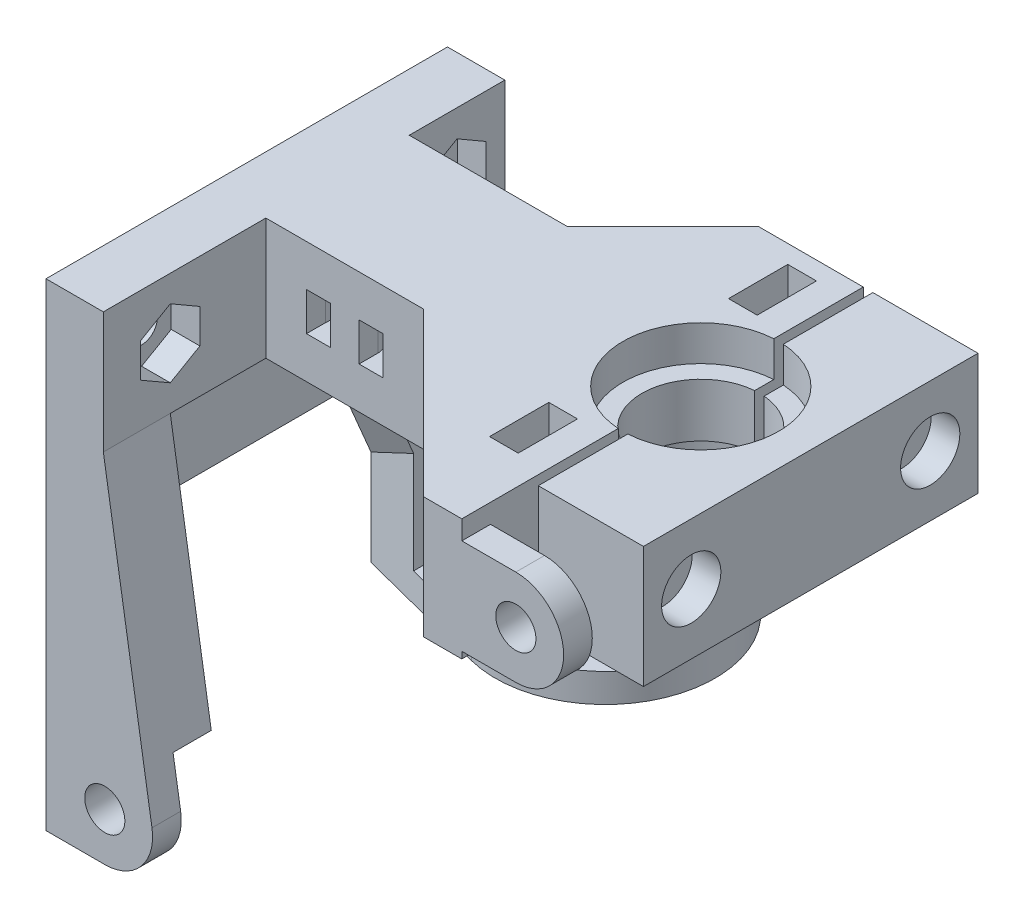
SolidWorks part; units mm, degrees
note: The reader was unsure of these and kept them because the rebuilt part matched: shared geometry of "草圖14<3>", "草圖43<3>", "草圖34<5>", "草圖48<3>".
ref_plane "前基準面" through (0, 0, 0) normal (0, 0, 1) x (1, 0, 0)
ref_plane "上基準面" through (0, 0, 0) normal (0, 1, 0) x (1, 0, 0)
ref_plane "右基準面" through (0, 0, 0) normal (1, 0, 0) x (0, 0, -1)
sketch "草圖13" plane through (0, 0, 0) normal (0, 1, 0) x (1, 0, 0)
  line L0 (0, 0) -> (44, 0) construction
  line L1 (0, 0) -> (0, 17.5)
  line L2 (0, 0) -> (0, -17.5)
  line L3 (0, 17.5) -> (6, 17.5)
  line L4 (6, 17.5) -> (6, -17.5)
  line L5 (6, -17.5) -> (0, -17.5)
  line L6 (6, 7.5) -> (32.5, 7.5)
  line L7 (6, -7.5) -> (32.5, -7.5)
  line L8 (32.5, 17.5) -> (22.5, 7.5)
  line L9 (32.5, -17.5) -> (55.5, -17.5)
  line L10 (32.5, -17.5) -> (32.5, 17.5)
  line L11 (32.5, 17.5) -> (55.5, 17.5)
  line L12 (55.5, -17.5) -> (55.5, 17.5)
  line L13 (32.5, -17.5) -> (55.5, 17.5) construction
  line L14 (32.5, 17.5) -> (55.5, -17.5) construction
  line L15 (32.5, -17.5) -> (22.5, -7.5)
  line L16 (32.5, 7.5) -> (22.5, 7.5)
  line L17 (22.5, -7.5) -> (32.5, -7.5)
  circle A0 centre (44, 0) radius 8.15
  circle A1 centre (44, 0) radius 6.15
  point P17 (44, 0)
  dimension "D4" = 35
  dimension "D5" = 12.3
  dimension "D6" = 23
  dimension "D1" = 16.3
  dimension "D2" = 35
  dimension "D3" = 6
  dimension "D7" = 15
  dimension "D8" = 10
  dimension "D9" = 44
extrude "填料-伸長4" add sketch "草圖13" against normal blind 12.7
sketch "草圖17" plane through (0, 0, 0) normal (0, 1, 0) x (1, 0, 0)
  circle A0 centre (44, 0) radius 6.15
  circle A1 centre (44, 0) radius 8.15
  circle A2 centre (44, 0) radius 6.15 construction
  circle A3 centre (44, 0) radius 8.15 construction
  circle M29 centre (44, 0) radius 6.15
ref_plane "平面4" through (44, 0, 0) normal (-1, 0, 0) x (0, 0, 1)
sketch "草圖14" plane through (55.5, 0, 0) normal (-1, 0, 0) x (0, 0, 1)
  line L0 (17.5, -6.35) -> (7.5, -6.35) construction
  line L3 (-7.5, -6.35) -> (-17.5, -6.35) construction
  line L5 (-17.5, -12.7) -> (-17.5, 0) construction
  line L6 (17.5, -12.7) -> (17.5, 0) construction
  line L9 (7.5, -12.7) -> (7.5, 0) construction
  line L10 (-7.5, -12.7) -> (-7.5, 0) construction
  circle A0 centre (-12.5, -6.35) radius 1.65
  circle A1 centre (12.5, -6.35) radius 1.65
  circle A2 centre (12.5, -6.35) radius 3.1
  circle A3 centre (-12.5, -6.35) radius 3.1
  dimension "D1" = 3.3
  dimension "D2" = 6.2
sketch "草圖15" plane through (44, 0, 0) normal (-1, 0, 0) x (0, 0, 1)
  line L1 (17.5, 0) -> (-17.5, 0)
  line L2 (17.5, 0) -> (17.5, -12.7)
  line L3 (17.5, -12.7) -> (-17.5, -12.7)
  line L4 (-17.5, 0) -> (-17.5, -12.7)
extrude "除料-伸長11" cut sketch "草圖15" against normal blind 0.5 and the other way blind 0.5
extrude "除料-伸長12" cut sketch "草圖14" along normal blind 3 contours A3 A0 | A2 A1
extrude "除料-伸長13" cut sketch "草圖14<3>" along normal blind 25 contours A0 | A1
sketch "草圖14<3>" plane through (55.5, 0, 0) normal (-1, 0, 0) x (0, 0, 1) same geometry as "草圖14"
ref_plane "平面5" through (37.5, 0, 0) normal (1, 0, 0) x (0, 0, -1)
sketch "草圖16" plane through (37.5, 0, 0) normal (1, 0, 0) x (0, 0, -1)
  line L0 (-17.5, 0) -> (17.5, 0) construction
  line L1 (-15.6, -12.7) -> (-9.4, -12.7)
  line L2 (-15.6, -12.7) -> (-15.6, 0)
  line L3 (-15.6, 0) -> (-9.4, 0)
  line L4 (-9.4, -12.7) -> (-9.4, 0)
  line L5 (-15.6, -12.7) -> (-9.4, 0) construction
  line L6 (-15.6, 0) -> (-9.4, -12.7) construction
  line L8 (9.4, -12.7) -> (15.6, -12.7)
  line L9 (9.4, -12.7) -> (9.4, 0)
  line L10 (9.4, 0) -> (15.6, 0)
  line L11 (15.6, -12.7) -> (15.6, 0)
  line L12 (9.4, -12.7) -> (15.6, 0) construction
  line L13 (9.4, 0) -> (15.6, -12.7) construction
  point P0 (-12.5, -6.35)
  point P8 (12.5, -6.35)
  dimension "D1" = 6.2
extrude "除料-伸長14" cut sketch "草圖16" along normal blind 3
extrude "除料-伸長30" cut sketch "草圖17" against normal blind 3.7 contours A1 M29
sketch "草圖18" plane through (0, -12.7, 0) normal (0, -1, 0) x (1, 0, 0)
  circle A0 centre (44, 0) radius 8.15
  circle A1 centre (44, 0) radius 8.15 construction
  circle A2 centre (44, 0) radius 6.15
  circle A3 centre (44, 0) radius 6.15 construction
  line M5 (43.5, 6.1296) -> (43.5, 17.5)
  line M17 (43.5, -17.5) -> (43.5, -6.1296)
  arc M18 (43.5, -6.1296) -> (43.5, 6.1296) centre (44, 0) cw
extrude "除料-伸長31" cut sketch "草圖18" against normal blind 3.4 contours A2 A0 M17 M5 | A0 M5 M17 M18
sketch "草圖19" plane through (0, 0, 0) normal (-1, 0, 0) x (0, 0, 1)
  line L0 (0, 0) -> (0, -12.7) construction
  line L1 (17.5, -12.7) -> (-17.5, -12.7) construction
  line L2 (-12.5, -6.35) -> (12.5, -6.35) construction
  circle A0 centre (-12.5, -6.35) radius 1.65
  circle A1 centre (12.5, -6.35) radius 1.65
  point P8 (0, -6.35)
  dimension "D2" = 3.3
  dimension "D1" = 25
extrude "除料-伸長32" cut sketch "草圖19" against normal up to surface (6 mm away) contours A0 up to face at (6, -6.35, 12.5)
sketch "草圖20" plane through (6, 0, 0) normal (1, 0, 0) x (0, 0, -1)
  line L1 (-12.5, -2.8282) -> (-15.55, -4.5891)
  line L2 (-15.55, -4.5891) -> (-15.55, -8.1109)
  line L3 (-15.55, -8.1109) -> (-12.5, -9.8718)
  line L4 (-12.5, -9.8718) -> (-9.45, -8.1109)
  line L5 (-9.45, -8.1109) -> (-9.45, -4.5891)
  line L6 (-9.45, -4.5891) -> (-12.5, -2.8282)
  line L7 (12.5, -2.8282) -> (9.45, -4.5891)
  line L8 (9.45, -4.5891) -> (9.45, -8.1109)
  line L9 (9.45, -8.1109) -> (12.5, -9.8718)
  line L10 (12.5, -9.8718) -> (15.55, -8.1109)
  line L11 (15.55, -8.1109) -> (15.55, -4.5891)
  line L12 (15.55, -4.5891) -> (12.5, -2.8282)
  circle A0 centre (-12.5, -6.35) radius 3.05 construction
  circle A1 centre (12.5, -6.35) radius 3.05 construction
  dimension "D1" = 6.1
extrude "除料-伸長33" cut sketch "草圖20" against normal blind 3 contours L11 L12 L7 L8 L9 L10
sketch "草圖21" plane through (0, -12.7, 0) normal (0, -1, 0) x (1, 0, 0)
  line L0 (0, -17.5) -> (6, -17.5) construction
  line L1 (0, 17.5) -> (3, 17.5)
  line L2 (0, 17.5) -> (0, -17.5)
  line L3 (0, -17.5) -> (3, -17.5)
  line L4 (3, 17.5) -> (3, -17.5)
  dimension "D1" = 3
extrude "填料-伸長5" add sketch "草圖21" along normal blind 10
ref_plane "平面6" through (0, 0, 24.5) normal (0, 0, 1) x (1, 0, 0)
sketch "草圖22" plane through (0, 0, 24.5) normal (0, 0, 1) x (1, 0, 0)
  line L0 (0, 0) -> (0, -50)
  line L1 (0, -50) -> (6.15, -50)
  line L2 (6.15, -45) -> (49.15, -45) construction
  line L3 (49.15, -45) -> (49.15, -7) construction
  line L4 (0, 0) -> (6, 0)
  line L5 (6, -12.7) -> (11.0861, -44.2031)
  line L6 (6, 0) -> (6, -12.7)
  line L8 (49.15, -2) -> (43.5, -2)
  line L10 (43.5, -12.7) -> (43.5, 0) construction
  line L11 (43.5, -2) -> (43.5, 0)
  line L13 (43.5, 0) -> (38, 0)
  line L14 (32.5, 0) -> (43.5, 0) construction
  line L15 (38, 0) -> (38, -12.7)
  line L16 (32.5, -12.7) -> (43.5, -12.7) construction
  line L17 (38, -12.7) -> (43.5, -12.7)
  line L18 (43.5, -12.7) -> (43.5, -12)
  line L19 (43.5, -12) -> (49.15, -12)
  circle A0 centre (49.15, -7) radius 2.1
  circle A1 centre (6.15, -45) radius 2.1
  circle A2 centre (6.15, -45) radius 5
  circle A3 centre (49.15, -7) radius 5
  dimension "D5" = 4.2
  dimension "D4" = 10
  dimension "D1" = 38
  dimension "D2" = 43
  dimension "D3" = 45
  dimension "D6" = 6.15
ref_plane "平面9" through (0, -6.35, 0) normal (0, 1, 0) x (1, 0, 0)
extrude "填料-伸長6" add sketch "草圖22" against normal up to surface (7 mm away)
sketch "草圖41" plane through (0, 0, 17.5) normal (0, 0, -1) x (-1, 0, 0)
  line L1 (-13.6797, -50.7245) -> (1.3797, -50.7245)
  line L2 (-13.6797, -50.7245) -> (-13.6797, -39.2755)
  line L3 (-13.6797, -39.2755) -> (1.3797, -39.2755)
  line L4 (1.3797, -50.7245) -> (1.3797, -39.2755)
  line L5 (-13.6797, -50.7245) -> (1.3797, -39.2755) construction
  line L6 (-13.6797, -39.2755) -> (1.3797, -50.7245) construction
  point P0 (-6.15, -45)
extrude "除料-伸長34" cut sketch "草圖41" against normal blind 4
sketch "草圖42" plane through (0, -2, 0) normal (0, 1, 0) x (1, 0, 0)
  line L0 (54.15, -24.5) -> (54.15, -17.5) construction
  line L1 (43.5, -17.5) -> (54.15, -17.5)
  line L2 (43.5, -17.5) -> (43.5, -21.5)
  line L3 (43.5, -21.5) -> (54.15, -21.5)
  line L4 (54.15, -17.5) -> (54.15, -21.5)
  dimension "D1" = 4
extrude "除料-伸長35" cut sketch "草圖42" against normal up to surface (10 mm away) up to face at (45.96, -12, 20.3)
sketch "草圖43" plane through (0, 0, 0) normal (0, 1, 0) x (1, 0, 0)
  line L0 (32.5, -17.5) -> (39.5, -24.5)
  line L1 (43.5, -24.5) -> (38, -24.5) construction
  line L2 (39.5, -24.5) -> (32.5, -24.5)
  line L3 (32.5, -17.5) -> (32.5, -24.5)
  line L4 (32.5, -17.5) -> (38, -17.5)
  line L5 (38, -17.5) -> (38, -23)
  line L6 (38, -17.5) -> (38, -24.5) construction
  line L7 (32.5, -17.5) -> (22.5, -7.5) construction
  line M16 (32.5, -17.5) -> (38, -17.5)
  line M17 (38, -17.5) -> (38, -24.5)
  line M18 (38, -24.5) -> (43.5, -24.5)
extrude "除料-伸長36" cut sketch "草圖43" against normal up to surface (12.7 mm away) contours L0 M17 M18 up to face at (23.8969, -12.7, 1.9688)
extrude "填料-伸長7" add sketch "草圖43<3>" against normal up to surface (12.7 mm away) contours L0 M16 M17 up to face at (39, -12.7, -12.5)
sketch "草圖43<3>" plane through (0, 0, 0) normal (0, 1, 0) x (1, 0, 0) same geometry as "草圖43"
sketch "草圖34" plane through (6, 0, 0) normal (1, 0, 0) x (0, 0, -1)
  line L0 (17.5, -12.7) -> (9.5, -12.7)
  line L1 (9.5, -22.7) -> (9.5, -42.7)
  line L2 (9.5, -42.7) -> (24.5, -42.7)
  line L3 (17.5, -16.2009) -> (24.5, -32.7)
  line L4 (17.5, -12.7) -> (8.1346, -12.7) construction
  line L5 (9.5, -12.7) -> (9.5, -22.7)
  line L6 (9.5, -32.7) -> (5.2574, -22.7)
  line L7 (17.5, -12.7) -> (24.5, -12.7)
  line L8 (24.5, -12.7) -> (24.5, -42.7)
  line L9 (17.5, -22.7) -> (-17.5, -22.7) construction
  line L10 (5.2574, -22.7) -> (9.5, -22.7)
  line L11 (17.5, -22.7) -> (17.5, -12.7) construction
  line L12 (-17.5, -12.7) -> (17.5, -12.7) construction
  line L13 (5.2574, -22.7) -> (5.2574, -12.7)
  line L14 (-8.1346, -12.7) -> (8.1346, -12.7) construction
  line L15 (5.2574, -12.7) -> (9.5, -12.7)
  line L16 (9.5, -12.7) -> (9.4752, -12.712)
  line L17 (17.5, -12.7) -> (17.5, -16.2009)
  line L18 (9.5, -22.7) -> (17.5, -22.7)
  line L19 (17.5, -22.7) -> (17.5, -16.2009)
  dimension "D1" = 20
  dimension "D2" = 3.5009
  dimension "D3" = 8
  dimension "D4" = 10
  dimension "D5" = 20
  dimension "D6" = 7
extrude "填料-伸長8" add sketch "草圖34" against normal up to surface (6 mm away) contours L19 L18 L1 L2 L8 L3 | L10 L6 L1
sketch "草圖44" plane through (0, -42.7, 0) normal (0, -1, 0) x (1, 0, 0)
  line L0 (0, -24.5) -> (14.134, -28.1372)
  line L1 (0, -9.5) -> (14.134, -5.8628)
  line L2 (0, -9.5) -> (0, -24.5)
  line L5 (0, -9.5) -> (6, -9.5) construction
  line L6 (0, -24.5) -> (0, -9.5) construction
  circle A0 centre (17, -17) radius 11.5
  circle A1 centre (17, -17) radius 6.5
  line M1 (0, -9.5) -> (0, -24.5)
  line M2 (0, -24.5) -> (6, -24.5)
  line M3 (6, -24.5) -> (6, -9.5)
  line M4 (6, -9.5) -> (0, -9.5)
  dimension "D2" = 13
  dimension "D3" = 23
  dimension "D1" = 17
  dimension "D4" = 17
extrude "填料-伸長9" add sketch "草圖44" against normal blind 3 contours A0 A1 M3 | A0 M3 | A0 M3 M4 M1 M2 | A0 L0 M3 M2 | A0 L1 M4 M3
extrude "填料-伸長14" add sketch "草圖34<5>" against normal up to surface (3 mm away) up to face at (3, -19.9501, -6.7096)
sketch "草圖34<5>" plane through (6, 0, 0) normal (1, 0, 0) x (0, 0, -1) same geometry as "草圖34"
sketch "草圖39" plane through (0, -6.35, 0) normal (0, 1, 0) x (1, 0, 0)
  line L0 (6, -7.5) -> (14.25, -7.5) construction
  line L1 (6, -7.5) -> (22.5, -7.5) construction
  line L2 (14.25, -7.5) -> (14.25, -5.5) construction
  line L3 (12.75, -5.5) -> (12.75, -7.5)
  line L4 (15.75, -5.5) -> (15.75, -7.5)
  line L5 (10.25, -5.5) -> (10.25, -7.5)
  line L6 (13.25, -5.5) -> (13.25, -7.5)
  line L7 (18.25, -5.5) -> (18.25, -7.5)
  line L8 (15.75, -7.5) -> (18.25, -7.5)
  line L9 (10.25, -7.5) -> (12.75, -7.5)
  circle A0 centre (14.25, -5.5) radius 1.5
  circle A1 centre (14.25, -5.5) radius 4
  dimension "D2" = 3
  dimension "D1" = 2
  dimension "D3" = 2.5
extrude "除料-伸長37" cut sketch "草圖39" against normal blind 2 and the other way blind 2 contours L8 A1 L9 L3 A0 L4 | A1 L5 L9 | A1 L8 L7
sketch "草圖46" plane through (52.5, 0, 0) normal (1, 0, 0) x (0, 0, -1)
  circle A0 centre (-12.5, -6.35) radius 1.65
  circle A1 centre (12.5, -6.35) radius 1.65
extrude "填料-伸長12" add sketch "草圖46" against normal blind 0.2
sketch "草圖47" plane through (40.5, 0, 0) normal (-1, 0, 0) x (0, 0, 1)
  circle A0 centre (12.5, -6.35) radius 1.65
  circle A1 centre (-12.5, -6.35) radius 1.65
extrude "填料-伸長13" add sketch "草圖47" against normal blind 0.2
sketch "草圖48" plane through (0, -39.7, 0) normal (0, 1, 0) x (1, 0, 0)
  line L0 (6, 24.5) -> (6, 26.044)
  line L1 (0, 24.5) -> (14.134, 28.1372) construction
  line L2 (6, 26.044) -> (0, 24.5)
  line L3 (0, 24.5) -> (6, 24.5)
  line L4 (0, 9.5) -> (6, 7.956)
  line L5 (6, 17.5) -> (6, 7.5) construction
  line L6 (0, 9.5) -> (14.134, 5.8628) construction
  line L7 (6, 7.956) -> (6, 9.5)
  line L8 (0, 9.5) -> (6, 9.5)
  line M1 (6, 9.5) -> (0, 9.5)
  line M2 (0, 9.5) -> (14.134, 5.8628)
  line M4 (14.134, 28.1372) -> (0, 24.5)
  line M5 (0, 24.5) -> (6, 24.5)
extrude "填料-伸長15" add sketch "草圖48" along normal up to surface (3.3608 mm away) contours L0 M5 M4
extrude "填料-伸長16" add sketch "草圖48<3>" along normal up to surface (7 mm away) contours L7 M2 M1
sketch "草圖48<3>" plane through (0, -39.7, 0) normal (0, 1, 0) x (1, 0, 0) same geometry as "草圖48"
sketch "草圖49" plane through (0, 0, 0) normal (-1, 0, 0) x (0, 0, 1)
  line L0 (-12.5, -6.35) -> (17.5, -6.35) construction
  circle A0 centre (17.5, -6.35) radius 1.65
  circle A1 centre (-12.5, -6.35) radius 1.65 construction
  dimension "D1" = 30
extrude "除料-伸長38" cut sketch "草圖49" against normal up to surface (6 mm away) up to face at (6, -7.62, 16.3)
sketch "草圖50" plane through (6, 0, 0) normal (1, 0, 0) x (0, 0, -1)
  line L0 (-17.5, -12.7) -> (-17.5, 0) construction
  line L1 (-17.5, -2.7704) -> (-20.6, -4.5602)
  line L2 (-20.6, -4.5602) -> (-20.6, -8.1398)
  line L3 (-20.6, -8.1398) -> (-17.5, -9.9296)
  line L4 (-17.5, -9.9296) -> (-14.4, -8.1398)
  line L5 (-14.4, -8.1398) -> (-14.4, -4.5602)
  line L6 (-14.4, -4.5602) -> (-17.5, -2.7704)
  circle A0 centre (-17.5, -6.35) radius 3.1 construction
  circle A1 centre (12.5, -6.35) radius 3.1 construction
  circle M3 centre (-17.5, -6.35) radius 1.65
extrude "除料-伸長39" cut sketch "草圖50" against normal up to surface (3 mm away) contours L5 L6 L1 L2 L3 L4 M3 up to face at (3, -6.35, -12.5)
